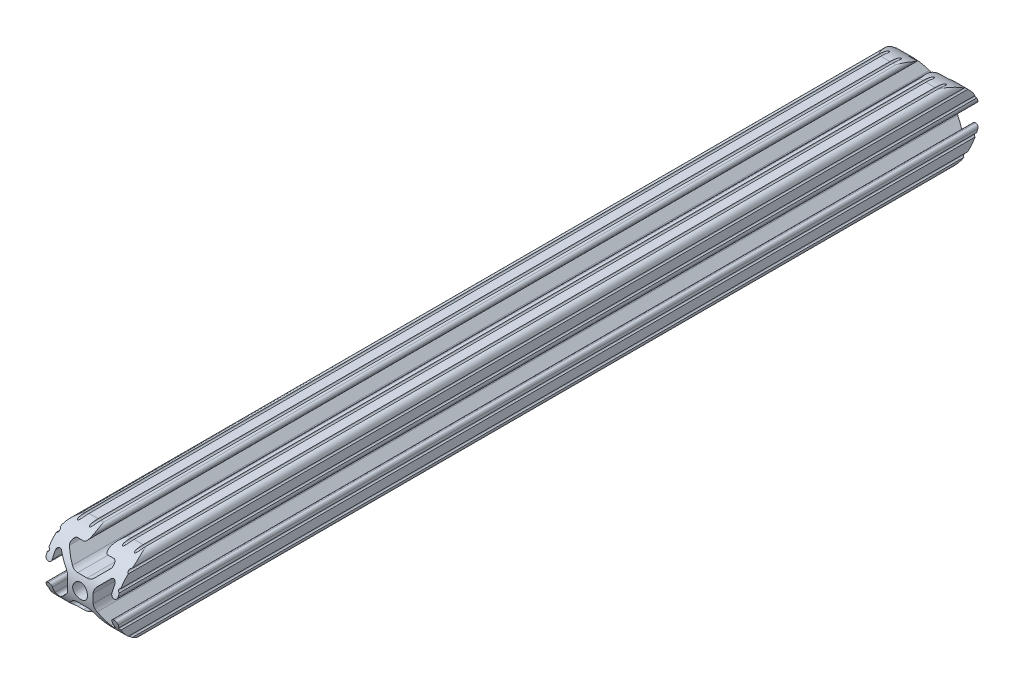
SolidWorks part; units mm, degrees
material "6061-T6 (SS)"
ref_plane "Front Plane" through (0, 0, 0) normal (0, 0, 1) x (1, 0, 0)
ref_plane "Top Plane" through (0, 0, 0) normal (0, 1, 0) x (1, 0, 0)
ref_plane "Right Plane" through (0, 0, 0) normal (1, 0, 0) x (0, 0, -1)
sketch "Sketch1" plane through (0, 0, 0) normal (0, 0, 1) x (1, 0, 0)
  line L88 (-7.1797, -8.6452) -> (-3.9523, -5.4237)
  line L89 (-1.7093, -4.4958) -> (1.7093, -4.4958)
  line L90 (3.9523, -5.4237) -> (7.1797, -8.6452)
  line L91 (6.4164, -10.4902) -> (4.2875, -10.4902)
  line L92 (3.2385, -11.5392) -> (3.2385, -11.651)
  line L93 (4.2875, -12.7) -> (5.3171, -12.7)
  line L94 (6.3331, -12.7) -> (9.5504, -12.7)
  line L95 (12.7, -9.5504) -> (12.7, -6.3331)
  line L96 (12.7, -5.3171) -> (12.7, -4.2875)
  line L97 (11.651, -3.2385) -> (11.5392, -3.2385)
  line L98 (10.4902, -4.2875) -> (10.4902, -6.4021)
  line L99 (8.7371, -7.1294) -> (5.441, -3.8408)
  line L100 (4.5085, -1.5932) -> (4.5085, 1.5932)
  line L101 (5.441, 3.8408) -> (8.7371, 7.1294)
  line L102 (10.4902, 6.4021) -> (10.4902, 4.2875)
  line L103 (11.5392, 3.2385) -> (11.651, 3.2385)
  line L104 (12.7, 4.2875) -> (12.7, 5.3171)
  line L105 (12.7, 6.3331) -> (12.7, 9.5504)
  line L106 (9.5504, 12.7) -> (6.3331, 12.7)
  line L107 (5.3171, 12.7) -> (4.2875, 12.7)
  line L108 (3.2385, 11.651) -> (3.2385, 11.5392)
  line L109 (4.2875, 10.4902) -> (6.4768, 10.4902)
  line L110 (7.207, 8.7244) -> (3.8983, 5.4232)
  line L111 (1.6558, 4.4958) -> (-1.6558, 4.4958)
  line L112 (-3.8983, 5.4232) -> (-7.207, 8.7244)
  line L113 (-6.4768, 10.4902) -> (-4.2875, 10.4902)
  line L114 (-3.2385, 11.5392) -> (-3.2385, 11.651)
  line L115 (-4.2875, 12.7) -> (-5.3171, 12.7)
  line L116 (-6.3331, 12.7) -> (-9.5504, 12.7)
  line L117 (-12.7, 9.5504) -> (-12.7, 6.3331)
  line L118 (-12.7, 5.3171) -> (-12.7, 4.2875)
  line L119 (-11.651, 3.2385) -> (-11.5392, 3.2385)
  line L120 (-10.4902, 4.2875) -> (-10.4902, 6.4021)
  line L121 (-8.7371, 7.1294) -> (-5.441, 3.8408)
  line L122 (-4.5085, 1.5932) -> (-4.5085, -1.5932)
  line L123 (-5.441, -3.8408) -> (-8.7371, -7.1294)
  line L124 (-10.4902, -6.4021) -> (-10.4902, -4.2875)
  line L125 (-11.5392, -3.2385) -> (-11.651, -3.2385)
  line L126 (-12.7, -4.2875) -> (-12.7, -5.3171)
  line L127 (-12.7, -6.3331) -> (-12.7, -9.5504)
  line L128 (-9.5504, -12.7) -> (-6.3331, -12.7)
  line L129 (-5.3171, -12.7) -> (-4.2875, -12.7)
  line L130 (-3.2385, -11.651) -> (-3.2385, -11.5392)
  line L131 (-4.2875, -10.4902) -> (-6.4164, -10.4902)
  circle A1 centre (0, 0) radius 2.6035
  arc A104 (-7.1797, -8.6452) -> (-6.4164, -10.4902) centre (-6.4164, -9.4098) ccw
  arc A105 (-1.7093, -4.4958) -> (-3.9523, -5.4237) centre (-1.7093, -7.6708) ccw
  arc A106 (3.9523, -5.4237) -> (1.7093, -4.4958) centre (1.7093, -7.6708) ccw
  arc A107 (6.4164, -10.4902) -> (7.1797, -8.6452) centre (6.4164, -9.4098) ccw
  arc A108 (4.2875, -10.4902) -> (3.2385, -11.5392) centre (4.2875, -11.5392) ccw
  arc A109 (3.2385, -11.651) -> (4.2875, -12.7) centre (4.2875, -11.651) ccw
  arc A110 (6.3331, -12.7) -> (5.3171, -12.7) centre (5.8251, -12.7) ccw
  arc A111 (10.5664, -12.6998) -> (9.5504, -12.7) centre (10.0584, -12.7) ccw
  arc A112 (10.5664, -12.6998) -> (12.6998, -10.5664) centre (10.5918, -10.5918) ccw
  arc A113 (12.7, -9.5504) -> (12.6998, -10.5664) centre (12.7, -10.0584) ccw
  arc A114 (12.7, -5.3171) -> (12.7, -6.3331) centre (12.7, -5.8251) ccw
  arc A115 (12.7, -4.2875) -> (11.651, -3.2385) centre (11.651, -4.2875) ccw
  arc A116 (11.5392, -3.2385) -> (10.4902, -4.2875) centre (11.5392, -4.2875) ccw
  arc A117 (8.7371, -7.1294) -> (10.4902, -6.4021) centre (9.4628, -6.4021) ccw
  arc A118 (4.5085, -1.5932) -> (5.441, -3.8408) centre (7.6835, -1.5932) ccw
  arc A119 (5.441, 3.8408) -> (4.5085, 1.5932) centre (7.6835, 1.5932) ccw
  arc A120 (10.4902, 6.4021) -> (8.7371, 7.1294) centre (9.4628, 6.4021) ccw
  arc A121 (10.4902, 4.2875) -> (11.5392, 3.2385) centre (11.5392, 4.2875) ccw
  arc A122 (11.651, 3.2385) -> (12.7, 4.2875) centre (11.651, 4.2875) ccw
  arc A123 (12.7, 6.3331) -> (12.7, 5.3171) centre (12.7, 5.8251) ccw
  arc A124 (12.6998, 10.5664) -> (12.7, 9.5504) centre (12.7, 10.0584) ccw
  arc A125 (12.6998, 10.5664) -> (10.5664, 12.6998) centre (10.5918, 10.5918) ccw
  arc A126 (9.5504, 12.7) -> (10.5664, 12.6998) centre (10.0584, 12.7) ccw
  arc A127 (5.3171, 12.7) -> (6.3331, 12.7) centre (5.8251, 12.7) ccw
  arc A128 (4.2875, 12.7) -> (3.2385, 11.651) centre (4.2875, 11.651) ccw
  arc A129 (3.2385, 11.5392) -> (4.2875, 10.4902) centre (4.2875, 11.5392) ccw
  arc A130 (7.207, 8.7244) -> (6.4768, 10.4902) centre (6.4768, 9.4563) ccw
  arc A131 (1.6558, 4.4958) -> (3.8983, 5.4232) centre (1.6558, 7.6708) ccw
  arc A132 (-3.8983, 5.4232) -> (-1.6558, 4.4958) centre (-1.6558, 7.6708) ccw
  arc A133 (-6.4768, 10.4902) -> (-7.207, 8.7244) centre (-6.4768, 9.4563) ccw
  arc A134 (-4.2875, 10.4902) -> (-3.2385, 11.5392) centre (-4.2875, 11.5392) ccw
  arc A135 (-3.2385, 11.651) -> (-4.2875, 12.7) centre (-4.2875, 11.651) ccw
  arc A136 (-6.3331, 12.7) -> (-5.3171, 12.7) centre (-5.8251, 12.7) ccw
  arc A137 (-10.5664, 12.6998) -> (-9.5504, 12.7) centre (-10.0584, 12.7) ccw
  arc A138 (-10.5664, 12.6998) -> (-12.6998, 10.5664) centre (-10.5918, 10.5918) ccw
  arc A139 (-12.7, 9.5504) -> (-12.6998, 10.5664) centre (-12.7, 10.0584) ccw
  arc A140 (-12.7, 5.3171) -> (-12.7, 6.3331) centre (-12.7, 5.8251) ccw
  arc A141 (-12.7, 4.2875) -> (-11.651, 3.2385) centre (-11.651, 4.2875) ccw
  arc A142 (-11.5392, 3.2385) -> (-10.4902, 4.2875) centre (-11.5392, 4.2875) ccw
  arc A143 (-8.7371, 7.1294) -> (-10.4902, 6.4021) centre (-9.4628, 6.4021) ccw
  arc A144 (-4.5085, 1.5932) -> (-5.441, 3.8408) centre (-7.6835, 1.5932) ccw
  arc A145 (-5.441, -3.8408) -> (-4.5085, -1.5932) centre (-7.6835, -1.5932) ccw
  arc A146 (-10.4902, -6.4021) -> (-8.7371, -7.1294) centre (-9.4628, -6.4021) ccw
  arc A147 (-10.4902, -4.2875) -> (-11.5392, -3.2385) centre (-11.5392, -4.2875) ccw
  arc A148 (-11.651, -3.2385) -> (-12.7, -4.2875) centre (-11.651, -4.2875) ccw
  arc A149 (-12.7, -6.3331) -> (-12.7, -5.3171) centre (-12.7, -5.8251) ccw
  arc A150 (-12.6998, -10.5664) -> (-12.7, -9.5504) centre (-12.7, -10.0584) ccw
  arc A151 (-12.6998, -10.5664) -> (-10.5664, -12.6998) centre (-10.5918, -10.5918) ccw
  arc A152 (-9.5504, -12.7) -> (-10.5664, -12.6998) centre (-10.0584, -12.7) ccw
  arc A153 (-5.3171, -12.7) -> (-6.3331, -12.7) centre (-5.8251, -12.7) ccw
  arc A154 (-4.2875, -12.7) -> (-3.2385, -11.651) centre (-4.2875, -11.651) ccw
  arc A155 (-3.2385, -11.5392) -> (-4.2875, -10.4902) centre (-4.2875, -11.5392) ccw
extrude "Boss-Extrude1" add sketch "Sketch1" along normal mid plane 304.8
sketch "Sketch3" plane through (12.7, 0, 0) normal (1, 0, 0) x (0, 0, -1)
  line L0 (-152.4, 0) -> (152.4, 0) construction
  line L1 (-152.4, 12.7) -> (152.4, 12.7)
  line L2 (-152.4, 12.7) -> (-152.4, -12.7)
  line L3 (-152.4, -12.7) -> (152.4, -12.7)
  line L4 (152.4, 12.7) -> (152.4, -12.7)
  circle A0 centre (-139.7, 0) radius 12.7
  circle A1 centre (139.7, 0) radius 12.7
  circle A2 centre (-139.7, 0) radius 3.175
  circle A3 centre (-114.3, 0) radius 3.175
  line M9 (152.4, 6.3331) -> (152.4, 9.5504)
  line M10 (152.4, 9.5504) -> (-152.4, 9.5504)
  line M11 (-152.4, 9.5504) -> (-152.4, 6.3331)
  line M12 (-152.4, 6.3331) -> (152.4, 6.3331)
  dimension "D1" = 25.4
  dimension "D2" = 6.35
extrude "Cut-Extrude1" cut sketch "Sketch3" against normal through all both and the other way through all contours A0 L2 L3 | A0 M10 M11 M12 | A0 L1 L2 M10 | A0 L2 M12 | L0 A3 | A3 L0 | A2 L0 | L0 A2 | A1 L4 L1 M10 | A1 M12 M9 M10 | A1 L4 M12 | A1 L3 L4 region at (12.7, -1.3475, 139.7) region at (12.7, 1.3475, 139.7) region at (12.7, 1.3475, 114.3) region at (12.7, -1.3475, 114.3) region at (12.7, -9.8632, 149.5632) region at (12.7, 4.7717, 151.8989) region at (12.7, 8.1865, 150.8688) region at (12.7, -9.8632, -149.5632) region at (12.7, 11.3727, 148.6456) region at (12.7, 4.7717, -151.8989) region at (12.7, 8.1865, -150.8688) region at (12.7, 11.3727, -148.6456)
